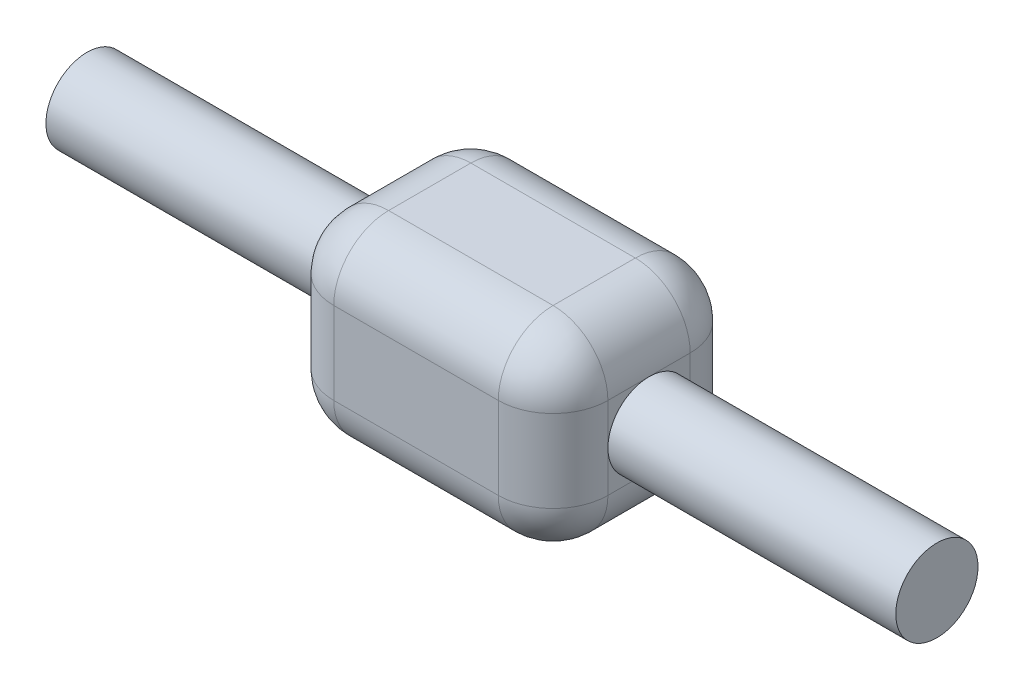
SolidWorks part; units mm, degrees
ref_plane "Front" through (0, 0, 0) normal (0, 0, 1) x (1, 0, 0)
ref_plane "Top" through (0, 0, 0) normal (0, 1, 0) x (1, 0, 0)
ref_plane "Right" through (0, 0, 0) normal (1, 0, 0) x (0, 0, -1)
sketch "草图2" plane through (0, 0, 0) normal (1, 0, 0) x (0, 0, -1)
  circle A0 centre (0, 0) radius 7.5
  dimension "D1" = 15
extrude "凸台-拉伸1" add sketch "草图2" along normal mid plane 155
sketch "草图3" plane through (0, 0, 0) normal (1, 0, 0) x (0, 0, -1)
  line L1 (17.5, -17.5) -> (-17.5, -17.5)
  line L2 (17.5, -17.5) -> (17.5, 17.5)
  line L3 (17.5, 17.5) -> (-17.5, 17.5)
  line L4 (-17.5, -17.5) -> (-17.5, 17.5)
  line L5 (17.5, -17.5) -> (-17.5, 17.5) construction
  line L6 (17.5, 17.5) -> (-17.5, -17.5) construction
  point P0 (0, 0)
  dimension "D1" = 35
  dimension "D2" = 35
extrude "凸台-拉伸2" add sketch "草图3" along normal mid plane 50
fillet "圆角1" radius 10 4 edges at (0, -17.5, -17.5) (0, 17.5, -17.5) (0, -17.5, 17.5) (0, 17.5, 17.5)
fillet "圆角2" radius 10 16 edges at (-25, 14.5711, -14.5711) (-25, 0, -17.5) (-25, -14.5711, -14.5711) (-25, -17.5, 0) (-25, -14.5711, 14.5711) (-25, 0, 17.5) (-25, 14.5711, 14.5711) (25, 14.5711, -14.5711) (25, 0, -17.5) (25, -14.5711, -14.5711) (25, -17.5, 0) (25, -14.5711, 14.5711) (25, 0, 17.5) (25, 14.5711, 14.5711) (-25, 17.5, 0) (25, 17.5, 0)
